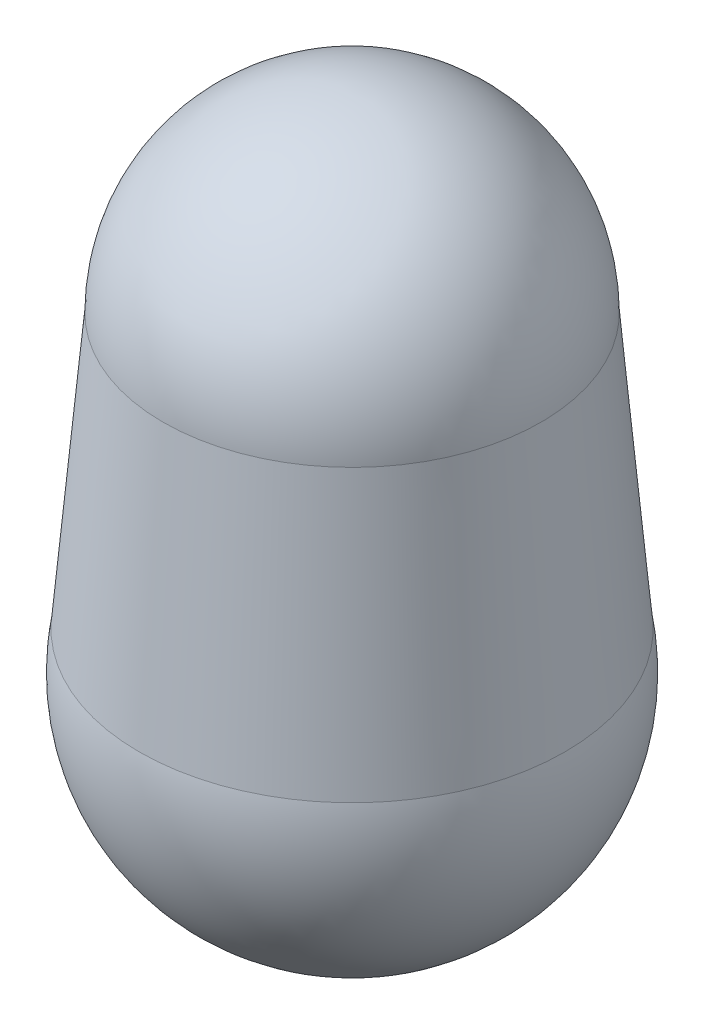
SolidWorks part; units mm, degrees
ref_plane "Front Plane" through (0, 0, 0) normal (0, 0, 1) x (1, 0, 0)
ref_plane "Top Plane" through (0, 0, 0) normal (0, 1, 0) x (1, 0, 0)
ref_plane "Right Plane" through (0, 0, 0) normal (1, 0, 0) x (0, 0, -1)
sketch "Sketch1" plane through (0, 0, 0) normal (0, 1, 0) x (1, 0, 0)
  line L0 (0, 6.95) -> (0, -6.95) construction
  line L1 (0, 6.95) -> (0, -6.95)
  arc A0 (0, -6.95) -> (0, 6.95) centre (0, 0) ccw
  dimension "D1" = 13.9
revolve "Revolve1" add sketch "Sketch1" angle 360 about L0
sketch "Sketch2" plane through (0, 0, 0) normal (0, 1, 0) x (1, 0, 0)
  circle A0 centre (0, 0) radius 6.95
  dimension "D1" = 13.9
extrude "Boss-Extrude1" add sketch "Sketch2" along normal blind 10 draft 5
sketch "Sketch3" plane through (0, 10, 0) normal (0, 1, 0) x (1, 0, 0)
  line L0 (0, 6.0751) -> (0, -6.0751) construction
  line L1 (0, 6.0751) -> (0, -6.0751)
  arc A0 (0, -6.0751) -> (0, 6.0751) centre (0, 0) ccw
revolve "Revolve2" add sketch "Sketch3" angle 360 about L0
